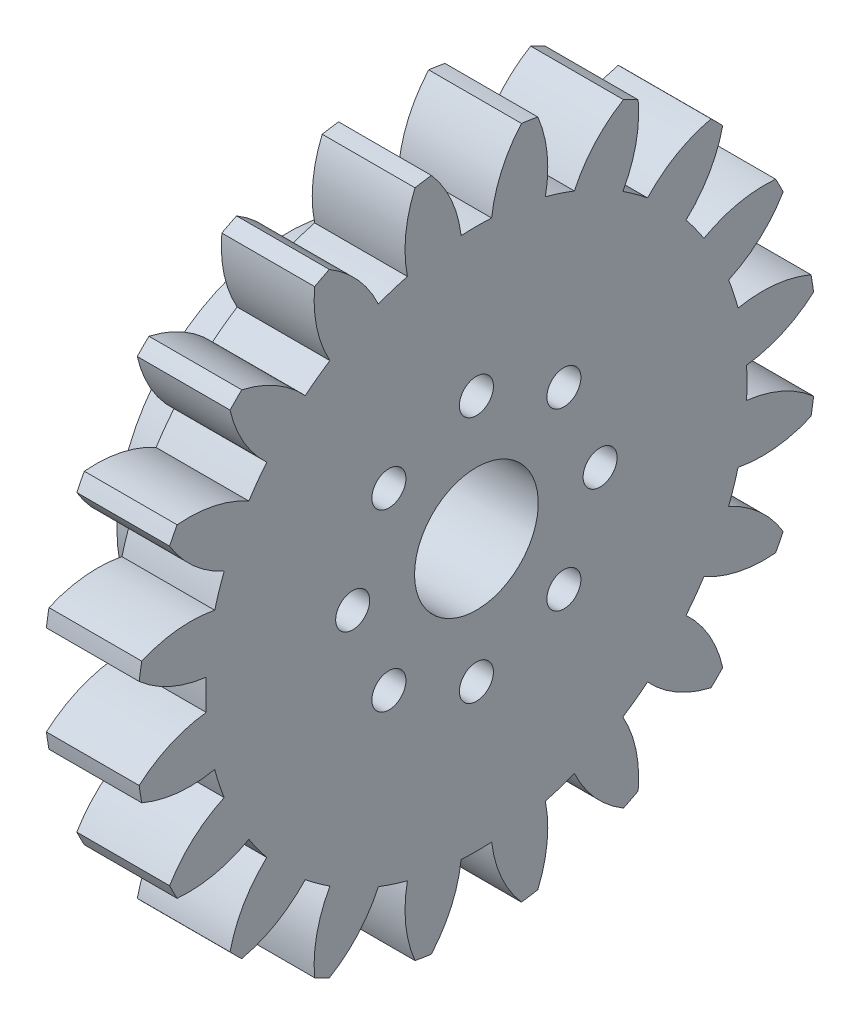
SolidWorks part; units mm, degrees
material "6061 Alloy"
ref_plane "Plane1" through (0, 0, 0) normal (0, 0, 1) x (1, 0, 0)
ref_plane "Plane2" through (0, 0, 0) normal (0, 1, 0) x (1, 0, 0)
ref_plane "Plane3" through (0, 0, 0) normal (1, 0, 0) x (0, 0, -1)
other "Configuration Table"
sketch "HoldingSke" plane through (0, 0, 0) normal (0, 1, 0) x (1, 0, 0)
  line L0 (0, 0) -> (0.4698, -0.171)
  line L1 (-15, 0) -> (100, 0) construction
  line L2 (0, 0) -> (-2.1039, 2.3779)
  line L3 (0, 0) -> (-11.863, 4.5341)
  line L4 (0, 0) -> (8.1152, 2.9537)
  line L5 (0, 0) -> (-11.4777, -4.2808)
  line L6 (0, 0) -> (-4.9738, -3.3558)
  line L7 (-2.1039, 2.3779) -> (0.5329, 14.3408)
  line L8 (-76.2, 54.61) -> (-74.8, 54.61)
  line L9 (-71.009, 38.7566) -> (-53.1078, 45.2721)
  line L10 (-76.2, 71.12) -> (104.1128, 71.12)
  line L11 (0, 0) -> (-6, 0)
  line L12 (-76.2, 101.6) -> (-76.133, 101.6)
  line L13 (24.9733, 27.94) -> (52.9518, 28.4284)
  line L14 (24.9733, 27.94) -> (24.9743, 27.94)
  line L15 (24.9733, 27.94) -> (100.4006, 29.5858)
  line L16 (-63.627, -2) -> (-12.827, -2)
  circle A0 centre (0, 0) radius 4
  circle A1 centre (0, 0) radius 11
  circle A2 centre (0, 0) radius 11
  circle A3 centre (0, 0) radius 4
  dimension "Num_teeth" = 20
  dimension "Pitch_radius" = 180.3128
  dimension "Width" = 6
  dimension "Thickness" = 6
sketch "BasProSke" plane through (0, 0, 0) normal (0, 1, 0) x (1, 0, 0)
  line L0 (-10, 0) -> (60, 0) construction
  line L1 (0, 0) -> (0, 22)
  line L2 (0, 0) -> (6, 0)
  line L3 (6, 0) -> (6, 22)
  line L4 (6, 22) -> (0, 22)
  dimension "Thickness" = 6
  dimension "Diameter" = 44
revolve "Base-Revolve" add sketch "BasProSke" angle 360 about L0
sketch "TooCutSke" plane through (0, 0, 0) normal (1, 0, 0) x (0, 0, -1)
  line L1 (0, 0) -> (0, 107) construction
  line L2 (0, 0) -> (-1.6864, 19.9288) construction
  line L3 (0, 0) -> (-6.2409, 39.4033) construction
  line L4 (-1.6864, 19.9288) -> (-3.1204, 19.7016) construction
  arc A0 (0.9862, 17.4712) -> (-0.9862, 17.4712) centre (0, 0) ccw
  arc A1 (2.9329, 21.8293) -> (-2.9329, 21.8293) centre (0, 0) ccw
  circle A2 centre (0, 0) radius 20 construction
  circle A3 centre (0, 0) radius 18.7939 construction
  arc A4 (-0.9862, 17.4712) -> (-2.9329, 21.8293) centre (-8.9313, 16.536) ccw
  arc A5 (2.9329, 21.8293) -> (0.9862, 17.4712) centre (8.9313, 16.536) ccw
extrude "ToothCut" cut sketch "TooCutSke" along normal through all
fillet "Breaks" [suppressed] radius 0.04 tangent propagation no
fillet "RootFillets" [suppressed] radius 0.501
pattern_circular "TeethCuts" count 20 every 18 about axis through (-10, 0, 0) along (1, 0, 0) of "ToothCut", "RootFillets", "Breaks"
sketch "HubNeaOneSke" plane through (0, 0, 0) normal (-1, 0, 0) x (0, 0, 1)
  circle A0 centre (0, 0) radius 11
  dimension "Diameter" = 22
extrude "HubNearOne" add sketch "HubNeaOneSke" along normal blind 6.2501
sketch "HubNeaBotSke" plane through (0, 0, 0) normal (-1, 0, 0) x (0, 0, 1)
  circle A0 centre (0, 0) radius 11
  dimension "Diameter" = 22
extrude "HubNearBoth" [suppressed] add sketch "HubNeaBotSke" along normal blind 3.125
ref_plane "FarPln" through (6, 0, 0) normal (1, 0, 0) x (0, 0, -1)
sketch "HubFarSke" plane through (6, 0, 0) normal (1, 0, 0) x (0, 0, -1)
  circle A0 centre (0, 0) radius 11
  dimension "Diameter" = 22
extrude "HubFar" [suppressed] add sketch "HubFarSke" along normal blind 3.125
sketch "BorSke" plane through (0, 0, 0) normal (1, 0, 0) x (0, 0, -1)
  circle A0 centre (0, 0) radius 4
  dimension "Diameter" = 8
extrude "Bore" cut sketch "BorSke" along normal mid plane 24.5001
sketch "KeySke" plane through (0, 0, 0) normal (1, 0, 0) x (0, 0, -1)
  line L0 (-1.5, 0) -> (-1.5, 5.4)
  line L1 (-1.5, 5.4) -> (1.5, 5.4)
  line L2 (1.5, 5.4) -> (1.5, 0)
  line L3 (0, 0) -> (0, 34) construction
  line L4 (-1.5, 0) -> (1.5, 0)
  dimension "Width" = 3
extrude "Keyway" [suppressed] cut sketch "KeySke" along normal mid plane 24.5001
pattern_circular "Keyway2" [suppressed] count 2 every 90 about axis through (-10, 0, 0) along (1, 0, 0)
hole_wizard "M2 Clearance Hole1" positions "Sketch1" profile "Sketch2" hole size "M2" standard "ANSI Metric" end condition through all
sketch "Sketch1" plane through (6, 0, 0) normal (1, 0, 0) x (0, 0, -1)
  circle A0 centre (0, 0) radius 8
  circle A1 centre (0, 0) radius 8
  circle A2 centre (0, 0) radius 8
  circle A3 centre (0, 0) radius 8
  circle A4 centre (0, 0) radius 8
  circle A5 centre (0, 0) radius 8
  circle A6 centre (0, 0) radius 8
  circle A7 centre (0, 0) radius 8
  point P2 (0, 8)
  point P23 (0, 8)
  point P32 (5.6569, 5.6569)
  point P34 (8, 0)
  point P36 (5.6569, -5.6569)
  point P38 (0, -8)
  point P40 (-5.6569, -5.6569)
  point P42 (-8, 0)
  point P44 (-5.6569, 5.6569)
  dimension "D1" = 16
  dimension "D2" = 8
sketch "Sketch2" plane through (6, 8, 0) normal (0, 1, 0) x (0, 0, -1)
  line L0 (0, 0) -> (0, 12.2501)
  line L1 (0, 12.2501) -> (1.1, 12.2501)
  line L2 (1.1, 12.2501) -> (1.1, 0)
  line L5 (1.1, 0) -> (0, 0)
  line L11 (0, -6.35) -> (0, 107.95) construction
  dimension "Thru Hole Dia." = 2.2
  dimension "Thru Hole Depth" = 12.2501
equation "' \"Module@HoldingSke\" = 6.35"
equation "' \"Num_teeth@HoldingSke\" = 12"
equation "' \"Ap@HoldingSke\" =  20"
equation "' \"Ap@HoldingSke\" = 20"
equation "' \"Width@HoldingSke\" = 0.5 * 25.4"
equation "' \"Hub_dia@HoldingSke\"= 1 * 25.4"
equation "' \"Hub_dia@HoldingSke\" = 1 * 25.4"
equation "' \"Overall_len@HoldingSke\" = 1.0 * 25.4"
equation "' \"Bore@HoldingSke\" = 0.75 * 25.4"
equation "' \"T_dim@HoldingSke\" = 0.1 * 25.4"
equation "' \"Width@KeySke\" = 0.25 * 25.4"
equation "' \"Show_teeth@HoldingSke\" = 13"
equation "' \"Backlash@HoldingSke\" = 0.009 * 25.4"
equation "' \"Addendum_fac@HoldingSke\" = 1.0"
equation "' \"Dedendum_fac@HoldingSke\" = 1.25"
equation "' \"Dedendum_add@HoldingSke\" = 0.00005 * 25.4"
equation "' \"Clearance_fac@HoldingSke\" = 0.25"
equation "\"Pitch@HoldingSke\" = 1 / \"Module@HoldingSke\""
equation "\"Overcut_dia@TooCutSke\" = (\"Num_teeth@HoldingSke\" + 2 * \"Addendum_fac@HoldingSke\") / \"Pitch@HoldingSke\" + 0.002 * 25.4"
equation "\"Pitch_dia@TooCutSke\" = \"Num_teeth@HoldingSke\" / \"Pitch@HoldingSke\""
equation "\"Base_dia@TooCutSke\" = \"Num_teeth@HoldingSke\" / \"Pitch@HoldingSke\" * cos((\"Ap@HoldingSke\"  * 3.14159265 / 180))"
equation "\"Root_dia@TooCutSke\" = (\"Num_teeth@HoldingSke\" + 2) / \"Pitch@HoldingSke\" - 2 * (\"Addendum_fac@HoldingSke\" + \"Dedendum_fac@HoldingSke\") / \"Pitch@HoldingSke\" - \"Dedendum_add@HoldingSke\" * 2"
equation "\"Half_ang@TooCutSke\" = 180 / \"Num_teeth@HoldingSke\""
equation "\"Half_CT@TooCutSke\" = \"Num_teeth@HoldingSke\" / \"Pitch@HoldingSke\" * sin((3.14159265 / 2 / \"Num_teeth@HoldingSke\")) / 2 - 7 * \"Backlash@HoldingSke\" / 4"
equation "\"Flank_rad@TooCutSke\" = \"Num_teeth@HoldingSke\" / \"Pitch@HoldingSke\" / 5"
equation "\"Radius@RootFillets\" = \"Clearance_fac@HoldingSke\" / \"Pitch@HoldingSke\" + \"Dedendum_add@HoldingSke\""
equation "\"Break_rad@Breaks\" = 0.02 / \"Pitch@HoldingSke\""
equation "\"Thickness@HoldingSke\" = \"Width@HoldingSke\""
equation "\"OAL@HoldingSke\" = \"Thickness@HoldingSke\""
equation "\"MHD@HoldingSke\" = (\"Num_teeth@HoldingSke\" + 2) / \"Pitch@HoldingSke\" - 2 * (\"Addendum_fac@HoldingSke\" + \"Dedendum_fac@HoldingSke\")  / \"Pitch@HoldingSke\" - \"Dedendum_add@HoldingSke\" * 2"
equation "\"MBD@HoldingSke\" = (\"Num_teeth@HoldingSke\" + 2) / \"Pitch@HoldingSke\" - 2 * (\"Addendum_fac@HoldingSke\" + \"Dedendum_fac@HoldingSke\")  / \"Pitch@HoldingSke\" - \"Dedendum_add@HoldingSke\" * 2 - 0.002 * 25.4"
equation "\"MHD@HoldingSke\" = ((sgn( \"MHD@HoldingSke\" - \"Hub_dia@HoldingSke\" )-1)*( \"MHD@HoldingSke\" - \"Hub_dia@HoldingSke\" ))/-2+ \"Hub_dia@HoldingSke\""
equation "\"MBD@HoldingSke\" = ((sgn( \"MBD@HoldingSke\" - \"Bore@HoldingSke\" )-1)*( \"MBD@HoldingSke\" - \"Bore@HoldingSke\" ))/-2+ \"Bore@HoldingSke\""
equation "\"OAL@HoldingSke\" = ((sgn( \"OAL@HoldingSke\" - \"Overall_len@HoldingSke\" )+1)*( \"OAL@HoldingSke\" - \"Overall_len@HoldingSke\" ))/2 + \"Overall_len@HoldingSke\" + 0.000002 * 25.4"
equation "\"Num_teeth@TeethCuts\" = int( \"Show_teeth@HoldingSke\" ) + 1"
equation "\"Num_teeth@TeethCuts\" = ((sgn( \"Num_teeth@TeethCuts\" - \"Num_teeth@HoldingSke\" )-1)*( \"Num_teeth@TeethCuts\" - \"Num_teeth@HoldingSke\" ))/-2+ \"Num_teeth@HoldingSke\""
equation "\"Num_teeth@TeethCuts\" = ((sgn( \"Num_teeth@TeethCuts\" - 2.0)+1)*( \"Num_teeth@TeethCuts\" - 2.0))/2 +2.0"
equation "\"Angle@TeethCuts\" = 360.0 / \"Num_teeth@HoldingSke\""
equation "\"Diameter@BasProSke\" = (\"Num_teeth@HoldingSke\" + 2 * \"Addendum_fac@HoldingSke\") / \"Pitch@HoldingSke\""
equation "\"Thickness@BasProSke\"  = \"Thickness@HoldingSke\""
equation "' \"Fillet_rad@BasProSke\" =  \"Thickness@HoldingSke\" * 0.05"
equation "' \"Fillet_rad@BasProSke\" = \"Thickness@HoldingSke\" * 0.05"
equation "\"MHD@HoldingSke\" = ((sgn( \"MHD@HoldingSke\" - \"Root_dia@TooCutSke\" )-1)*( \"MHD@HoldingSke\" - \"Root_dia@TooCutSke\" ))/-2+ \"Root_dia@TooCutSke\""
equation "\"Diameter@HubNeaOneSke\" = \"MHD@HoldingSke\""
equation "\"Length@HubNearOne\" = \"OAL@HoldingSke\" - \"Thickness@BasProSke\""
equation "\"Diameter@HubNeaBotSke\" = \"MHD@HoldingSke\""
equation "\"Length@HubNearBoth\" = ( \"OAL@HoldingSke\" - \"Thickness@BasProSke\" ) / 2.0"
equation "\"Thickness@FarPln\" = \"Thickness@BasProSke\""
equation "\"Diameter@HubFarSke\" = \"MHD@HoldingSke\""
equation "\"Length@HubFar\" = ( \"OAL@HoldingSke\" - \"Thickness@BasProSke\" ) / 2.0"
equation "\"Diameter@BorSke\" = \"MBD@HoldingSke\""
equation "\"D1@Bore\" = \"OAL@HoldingSke\" * 2.0"
equation "\"D1@Keyway\" = \"OAL@HoldingSke\" * 2.0"
equation "\"Offset@KeySke\" = \"T_dim@HoldingSke\" + \"MBD@HoldingSke\" / 2.0"
